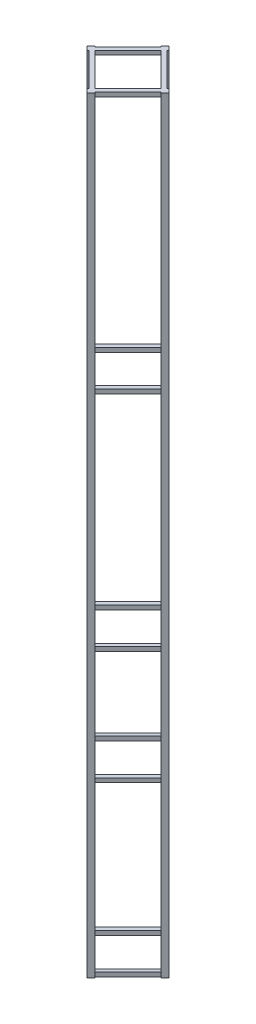
SolidWorks part; units mm, degrees
material "6061-T6 (SS)"
ref_plane "Front Plane" through (0, 0, 0) normal (0, 0, 1) x (1, 0, 0)
ref_plane "Top Plane" through (0, 0, 0) normal (0, 1, 0) x (1, 0, 0)
ref_plane "Right Plane" through (0, 0, 0) normal (1, 0, 0) x (0, 0, -1)
sketch "Sketch2" plane through (0, 0, 0) normal (0, 1, 0) x (1, 0, 0)
  line L0 (0, 94.7743) -> (-8.9803, 85.794)
  line L1 (-8.9803, 85.794) -> (-6.7352, 83.549)
  line L2 (-6.7352, 83.549) -> (0, 90.2842)
  line L3 (0, 90.2842) -> (6.7352, 83.549)
  line L4 (6.7352, 83.549) -> (8.9803, 85.794)
  line L5 (8.9803, 85.794) -> (0, 94.7743)
  line L6 (0, 0) -> (0, 186.644) construction
  line L7 (94.7743, 0) -> (85.794, 8.9803)
  line L8 (85.794, 8.9803) -> (83.549, 6.7352)
  line L9 (83.549, 6.7352) -> (90.2842, 0)
  line L10 (90.2842, 0) -> (83.549, -6.7352)
  line L11 (83.549, -6.7352) -> (85.794, -8.9803)
  line L12 (85.794, -8.9803) -> (94.7743, 0)
  line L13 (0, -94.7743) -> (8.9803, -85.794)
  line L14 (8.9803, -85.794) -> (6.7352, -83.549)
  line L15 (6.7352, -83.549) -> (0, -90.2842)
  line L16 (0, -90.2842) -> (-6.7352, -83.549)
  line L17 (-6.7352, -83.549) -> (-8.9803, -85.794)
  line L18 (-8.9803, -85.794) -> (0, -94.7743)
  line L19 (-94.7743, 0) -> (-85.794, -8.9803)
  line L20 (-85.794, -8.9803) -> (-83.549, -6.7352)
  line L21 (-83.549, -6.7352) -> (-90.2842, 0)
  line L22 (-90.2842, 0) -> (-83.549, 6.7352)
  line L23 (-83.549, 6.7352) -> (-85.794, 8.9803)
  line L24 (-85.794, 8.9803) -> (-94.7743, 0)
  point P31 (0, 0)
  dimension "D2" = 12.7
  dimension "D3" = 12.7
  dimension "D4" = 3.175
  dimension "D5" = 3.175
  dimension "D6" = 4
extrude "Boss-Extrude1" add sketch "Sketch2" along normal blind 1778
sketch "Sketch3" plane through (-45.1421, 0, -45.1421) normal (0.7071, 0, 0.7071) x (0.7071, 0, -0.7071)
  line L0 (-63.8405, 1778) -> (-63.8405, 0) construction
  line L1 (-54.3155, 0) -> (-63.8405, 0)
  line L2 (-54.3155, 0) -> (-54.3155, 9.525)
  line L3 (-54.3155, 9.525) -> (-63.8405, 9.525)
  line L4 (-63.8405, 0) -> (-63.8405, 9.525)
  dimension "D1" = 9.525
extrude "Boss-Extrude2" add sketch "Sketch3" along normal up to next (127.6811 mm away)
sketch "Sketch4" plane through (45.1421, 0, 45.1421) normal (-0.7071, 0, -0.7071) x (-0.7071, 0, 0.7071)
  line L0 (-54.3155, 1778) -> (-54.3155, 0) construction
  line L1 (-63.8405, 0) -> (-54.3155, 0)
  line L2 (-63.8405, 0) -> (-63.8405, 9.525)
  line L3 (-63.8405, 9.525) -> (-54.3155, 9.525)
  line L4 (-54.3155, 0) -> (-54.3155, 9.525)
  dimension "D1" = 9.525
extrude "Boss-Extrude3" add sketch "Sketch4" along normal up to next (127.6811 mm away)
sketch "Sketch5" plane through (38.4069, 0, -38.4069) normal (-0.7071, 0, 0.7071) x (0.7071, 0, 0.7071)
  line L0 (-67.0155, 0) -> (67.0155, 0) construction
  line L1 (-63.8405, 9.525) -> (-54.3155, 9.525)
  line L2 (-63.8405, 9.525) -> (-63.8405, 0)
  line L3 (-63.8405, 0) -> (-54.3155, 0)
  line L4 (-54.3155, 9.525) -> (-54.3155, 0)
  dimension "D1" = 9.525
extrude "Boss-Extrude4" add sketch "Sketch5" along normal up to next (108.6311 mm away)
sketch "Sketch6" plane through (-38.4069, 0, 38.4069) normal (0.7071, 0, -0.7071) x (-0.7071, 0, -0.7071)
  line L0 (-67.0155, 0) -> (54.3155, 0) construction
  line L1 (-63.8405, 9.525) -> (-54.3155, 9.525)
  line L2 (-63.8405, 9.525) -> (-63.8405, 0)
  line L3 (-63.8405, 0) -> (-54.3155, 0)
  line L4 (-54.3155, 9.525) -> (-54.3155, 0)
  dimension "D1" = 9.525
extrude "Boss-Extrude5" add sketch "Sketch6" along normal up to next
sketch "Sketch7" plane through (45.1421, 0, 45.1421) normal (-0.7071, 0, -0.7071) x (-0.7071, 0, 0.7071)
  line L0 (54.3155, 9.525) -> (54.3155, 390.525) construction
  line L1 (54.3155, 1778) -> (54.3155, 9.525) construction
  line L2 (63.8405, 1778) -> (63.8405, 9.525) construction
  line L3 (54.3155, 390.525) -> (63.8405, 390.525)
  line L4 (54.3155, 390.525) -> (54.3155, 400.05)
  line L5 (54.3155, 400.05) -> (63.8405, 400.05)
  line L6 (63.8405, 390.525) -> (63.8405, 400.05)
  dimension "D1" = 381
  dimension "D2" = 9.525
extrude "Boss-Extrude6" add sketch "Sketch7" along normal up to next
sketch "Sketch8" plane through (-38.4069, 0, 38.4069) normal (0.7071, 0, -0.7071) x (-0.7071, 0, -0.7071)
  line L0 (63.8405, 390.525) -> (-63.8405, 390.525) construction
  line L1 (-63.8405, 400.05) -> (-54.3155, 400.05)
  line L2 (-63.8405, 400.05) -> (-63.8405, 390.525)
  line L3 (-63.8405, 390.525) -> (-54.3155, 390.525)
  line L4 (-54.3155, 400.05) -> (-54.3155, 390.525)
  dimension "D1" = 9.525
extrude "Boss-Extrude7" add sketch "Sketch8" along normal up to next
sketch "Sketch9" plane through (38.4069, 0, 38.4069) normal (-0.7071, 0, -0.7071) x (-0.7071, 0, 0.7071)
  line L0 (-63.8405, 390.525) -> (54.3155, 390.525) construction
  line L1 (-63.8405, 400.05) -> (-54.3155, 400.05)
  line L2 (-63.8405, 400.05) -> (-63.8405, 390.525)
  line L3 (-63.8405, 390.525) -> (-54.3155, 390.525)
  line L4 (-54.3155, 400.05) -> (-54.3155, 390.525)
  dimension "D1" = 9.525
extrude "Boss-Extrude8" add sketch "Sketch9" along normal up to next
sketch "Sketch10" plane through (38.4069, 0, -38.4069) normal (-0.7071, 0, 0.7071) x (0.7071, 0, 0.7071)
  line L0 (-63.8405, 390.525) -> (54.3155, 390.525) construction
  line L1 (-63.8405, 400.05) -> (-54.3155, 400.05)
  line L2 (-63.8405, 400.05) -> (-63.8405, 390.525)
  line L3 (-63.8405, 390.525) -> (-54.3155, 390.525)
  line L4 (-54.3155, 400.05) -> (-54.3155, 390.525)
  dimension "D1" = 9.525
extrude "Boss-Extrude9" add sketch "Sketch10" along normal up to next
sketch "Sketch11" plane through (-45.1421, 0, -45.1421) normal (0.7071, 0, 0.7071) x (0.7071, 0, -0.7071)
  line L0 (-63.8405, 400.05) -> (-63.8405, 654.05) construction
  line L1 (-63.8405, 1778) -> (-63.8405, 400.05) construction
  line L2 (-54.3155, 1778) -> (-54.3155, 400.05) construction
  line L3 (-63.8405, 654.05) -> (-54.3155, 654.05)
  line L4 (-63.8405, 654.05) -> (-63.8405, 663.575)
  line L5 (-63.8405, 663.575) -> (-54.3155, 663.575)
  line L6 (-54.3155, 654.05) -> (-54.3155, 663.575)
  dimension "D1" = 254
  dimension "D2" = 9.525
extrude "Boss-Extrude10" add sketch "Sketch11" along normal up to next
sketch "Sketch12" plane through (-38.4069, 0, 38.4069) normal (0.7071, 0, -0.7071) x (-0.7071, 0, -0.7071)
  line L0 (-63.8405, 654.05) -> (63.8405, 654.05) construction
  line L1 (-63.8405, 663.575) -> (-54.3155, 663.575)
  line L2 (-63.8405, 663.575) -> (-63.8405, 654.05)
  line L3 (-63.8405, 654.05) -> (-54.3155, 654.05)
  line L4 (-54.3155, 663.575) -> (-54.3155, 654.05)
  dimension "D1" = 9.525
extrude "Boss-Extrude11" add sketch "Sketch12" along normal up to next
sketch "Sketch13" plane through (38.4069, 0, 38.4069) normal (-0.7071, 0, -0.7071) x (-0.7071, 0, 0.7071)
  line L0 (-63.8405, 654.05) -> (54.3155, 654.05) construction
  line L1 (-63.8405, 663.575) -> (-54.3155, 663.575)
  line L2 (-63.8405, 663.575) -> (-63.8405, 654.05)
  line L3 (-63.8405, 654.05) -> (-54.3155, 654.05)
  line L4 (-54.3155, 663.575) -> (-54.3155, 654.05)
  dimension "D1" = 9.525
extrude "Boss-Extrude12" add sketch "Sketch13" along normal up to next
sketch "Sketch14" plane through (38.4069, 0, -38.4069) normal (-0.7071, 0, 0.7071) x (0.7071, 0, 0.7071)
  line L0 (-63.8405, 654.05) -> (54.3155, 654.05) construction
  line L1 (-63.8405, 663.575) -> (-54.3155, 663.575)
  line L2 (-63.8405, 663.575) -> (-63.8405, 654.05)
  line L3 (-63.8405, 654.05) -> (-54.3155, 654.05)
  line L4 (-54.3155, 663.575) -> (-54.3155, 654.05)
  dimension "D1" = 9.525
extrude "Boss-Extrude13" add sketch "Sketch14" along normal up to next
sketch "Sketch15" plane through (45.1421, 0, -45.1421) normal (-0.7071, 0, 0.7071) x (0.7071, 0, 0.7071)
  line L0 (-63.8405, 663.575) -> (-63.8405, 1171.575) construction
  line L1 (-63.8405, 1778) -> (-63.8405, 663.575) construction
  dimension "D1" = 508
sketch "Sketch16" plane through (45.1421, 0, -45.1421) normal (-0.7071, 0, 0.7071) x (0.7071, 0, 0.7071)
  line L0 (-54.3155, 1778) -> (-54.3155, 663.575) construction
  line L1 (-63.8405, 1171.575) -> (-54.3155, 1171.575)
  line L2 (-63.8405, 1171.575) -> (-63.8405, 1181.1)
  line L3 (-63.8405, 1181.1) -> (-54.3155, 1181.1)
  line L4 (-54.3155, 1171.575) -> (-54.3155, 1181.1)
  dimension "D1" = 9.525
extrude "Boss-Extrude14" add sketch "Sketch16" along normal up to next
sketch "Sketch17" plane through (-38.4069, 0, -38.4069) normal (0.7071, 0, 0.7071) x (0.7071, 0, -0.7071)
  line L0 (-63.8405, 1171.575) -> (63.8405, 1171.575) construction
  line L1 (-63.8405, 1181.1) -> (-54.3155, 1181.1)
  line L2 (-63.8405, 1181.1) -> (-63.8405, 1171.575)
  line L3 (-63.8405, 1171.575) -> (-54.3155, 1171.575)
  line L4 (-54.3155, 1181.1) -> (-54.3155, 1171.575)
  dimension "D1" = 9.525
extrude "Boss-Extrude15" add sketch "Sketch17" along normal up to next
sketch "Sketch18" plane through (-38.4069, 0, 38.4069) normal (0.7071, 0, -0.7071) x (-0.7071, 0, -0.7071)
  line L0 (-63.8405, 1171.575) -> (54.3155, 1171.575) construction
  line L1 (-63.8405, 1181.1) -> (-54.3155, 1181.1)
  line L2 (-63.8405, 1181.1) -> (-63.8405, 1171.575)
  line L3 (-63.8405, 1171.575) -> (-54.3155, 1171.575)
  line L4 (-54.3155, 1181.1) -> (-54.3155, 1171.575)
  dimension "D1" = 9.525
extrude "Boss-Extrude16" add sketch "Sketch18" along normal up to next
sketch "Sketch19" plane through (38.4069, 0, 38.4069) normal (-0.7071, 0, -0.7071) x (-0.7071, 0, 0.7071)
  line L0 (-63.8405, 1171.575) -> (54.3155, 1171.575) construction
  line L1 (-63.8405, 1181.1) -> (-54.3155, 1181.1)
  line L2 (-63.8405, 1181.1) -> (-63.8405, 1171.575)
  line L3 (-63.8405, 1171.575) -> (-54.3155, 1171.575)
  line L4 (-54.3155, 1181.1) -> (-54.3155, 1171.575)
  dimension "D1" = 9.525
extrude "Boss-Extrude17" add sketch "Sketch19" along normal up to next
sketch "Sketch20" plane through (45.1421, 0, 45.1421) normal (-0.7071, 0, -0.7071) x (-0.7071, 0, 0.7071)
  line L0 (-63.8405, 1181.1) -> (-63.8405, 1790.7) construction
  line L1 (-63.8405, 1181.1) -> (-54.3155, 1181.1) construction
  line L2 (-63.8405, 1778) -> (-63.8405, 1181.1) construction
  dimension "D1" = 609.6
pattern_linear "LPattern1" count 2 spacing 1768.475 along (0, 1, 0) of "Boss-Extrude2", "Boss-Extrude3", "Boss-Extrude4", "Boss-Extrude5"
